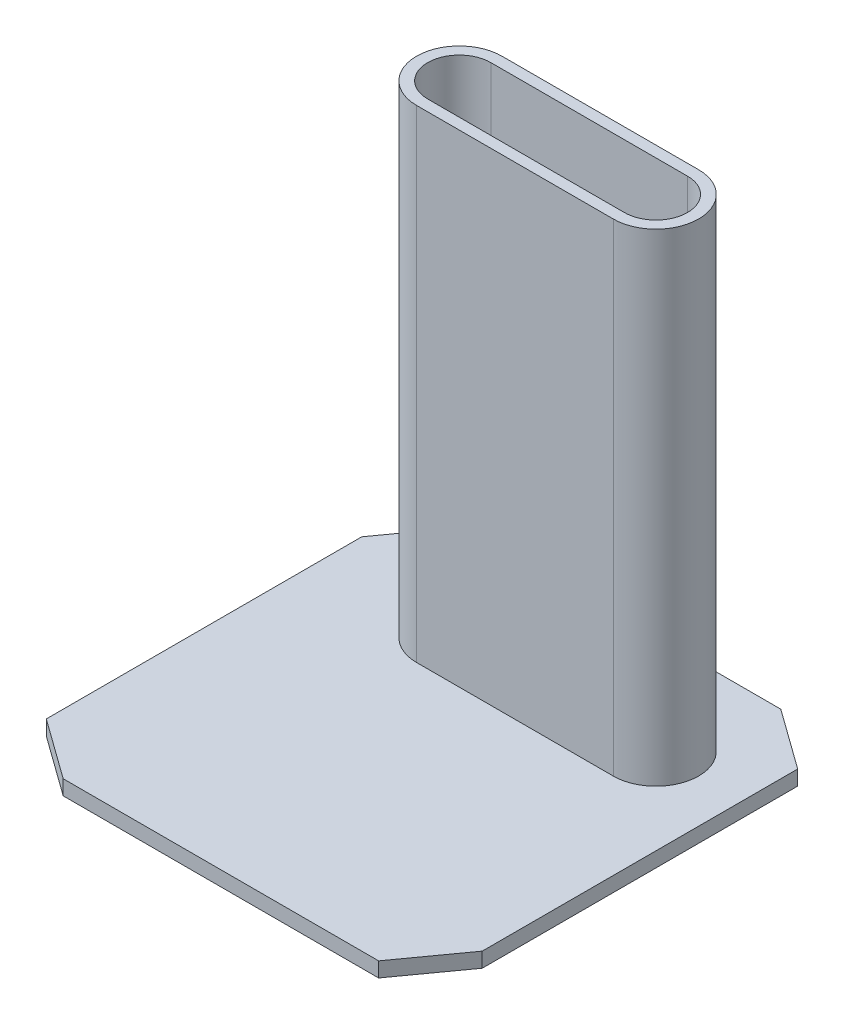
SolidWorks part; units mm, degrees
ref_plane "Front Plane" through (0, 0, 0) normal (0, 0, 1) x (1, 0, 0)
ref_plane "Top Plane" through (0, 0, 0) normal (0, 1, 0) x (1, 0, 0)
ref_plane "Right Plane" through (0, 0, 0) normal (1, 0, 0) x (0, 0, -1)
sketch "Sketch1" plane through (0, 0, 0) normal (0, 1, 0) x (1, 0, 0)
  line L0 (-73.4891, -86.2345) -> (11.5109, -86.2345)
  line L1 (11.5109, -86.2345) -> (23.1931, -70.001)
  line L2 (23.1931, -70.001) -> (23.1931, 14.999)
  line L3 (23.1931, 14.999) -> (6.9596, 26.6812)
  line L4 (6.9596, 26.6812) -> (-78.0404, 26.6812)
  line L5 (-78.0404, 26.6812) -> (-89.7226, 10.4477)
  line L6 (-89.7226, 10.4477) -> (-89.7226, -74.5523)
  line L7 (-89.7226, -74.5523) -> (-73.4891, -86.2345)
  dimension "D1" = 144.26
  dimension "D2" = 125.74
  dimension "D3" = 144.26
  dimension "D4" = 20
  dimension "D5" = 85
  dimension "D6" = 85
  dimension "D7" = 85
  dimension "D8" = 85
  dimension "D9" = 20
extrude "Boss-Extrude1" add sketch "Sketch1" along normal blind 4
sketch "Sketch2" plane through (0, 4, 0) normal (0, 1, 0) x (1, 0, 0)
  line L0 (-53, 0) -> (0, 0) construction
  line L1 (-53, 8.5) -> (0, 8.5)
  line L2 (-53, -8.5) -> (0, -8.5)
  line L3 (-53, 11.5) -> (0, 11.5)
  line L4 (-53, -11.5) -> (0, -11.5)
  arc A0 (-53, 8.5) -> (-53, -8.5) centre (-53, 0) ccw
  arc A1 (0, -8.5) -> (0, 8.5) centre (0, 0) ccw
  arc A2 (0, -11.5) -> (0, 11.5) centre (0, 0) ccw
  arc A3 (-53, 11.5) -> (-53, -11.5) centre (-53, 0) ccw
  point P3 (-26.5, 0)
  point P8 (-61.5, 0)
  point P9 (8.5, 0)
  dimension "D3" = 3
  dimension "D1" = 17
  dimension "D2" = 70
extrude "Boss-Extrude3" add sketch "Sketch2" along normal blind 130 contours L3 A2 L4 A3
sketch "Sketch3" plane through (0, 134, 0) normal (0, 1, 0) x (1, 0, 0)
  line L4 (-53, -8.5) -> (0, -8.5)
  line L5 (0, 8.5) -> (-53, 8.5)
  line L6 (-53, -8.5) -> (0, -8.5)
  line L7 (0, 8.5) -> (-53, 8.5)
  arc A4 (-53, 8.5) -> (-53, -8.5) centre (-53, 0) ccw
  arc A5 (0, -8.5) -> (0, 8.5) centre (0, 0) ccw
  arc A6 (-53, 8.5) -> (-53, -8.5) centre (-53, 0) ccw
  arc A7 (0, -8.5) -> (0, 8.5) centre (0, 0) ccw
  dimension "D1" = 3
extrude "Cut-Extrude1" cut sketch "Sketch3" against normal blind 130
